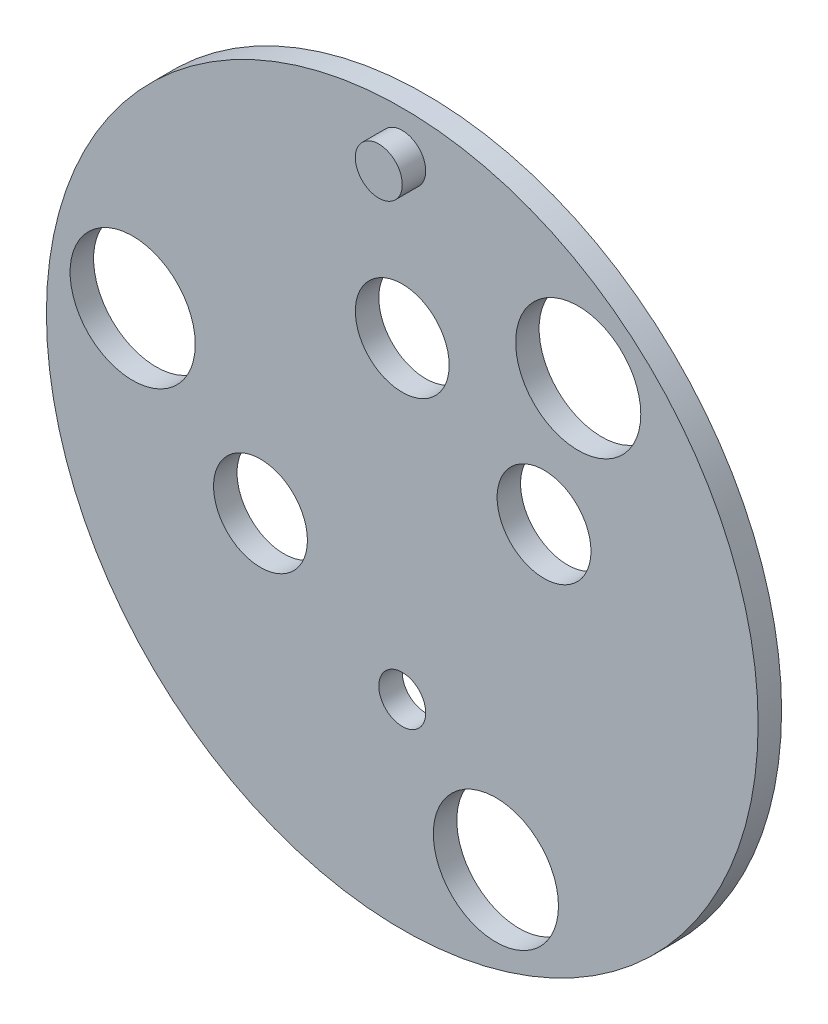
SolidWorks part; units mm, degrees
ref_plane "Front Plane" through (0, 0, 0) normal (0, 0, 1) x (1, 0, 0)
ref_plane "Top Plane" through (0, 0, 0) normal (0, 1, 0) x (1, 0, 0)
ref_plane "Right Plane" through (0, 0, 0) normal (1, 0, 0) x (0, 0, -1)
sketch "Sketch1" plane through (0, 0, 0) normal (0, 0, 1) x (1, 0, 0)
  circle A0 centre (0, 0) radius 227.5
  circle A1 centre (0, 200) radius 15
  point P5 (10.2659, 199.7364)
  dimension "D2" = 30
  dimension "D3" = 455
  dimension "D1" = 200
extrude "Boss-Extrude1" add sketch "Sketch1" along normal mid plane 15 contours A0
extrude "Boss-Extrude2" add sketch "Sketch1<3>" along normal blind 15 from surface contours A1 region at (0, 200, 0) starting at face at (227.5, 0, 7.5)
sketch "Sketch1<3>" plane through (0, 0, 0) normal (0, 0, 1) x (1, 0, 0) same geometry as "Sketch1"
sketch "Sketch2" plane through (0, 0, 7.5) normal (0, 0, 1) x (1, 0, 0)
  line L0 (90.6308, 42.2618) -> (-90.6308, -42.2618) construction
  line L1 (0, -100) -> (0, 100) construction
  line L2 (-172.3414, 30.3884) -> (0, 0) construction
  line L3 (59.8535, -164.4462) -> (0, 0) construction
  line L4 (0, 0) -> (112.4878, 134.0578) construction
  circle A0 centre (-172.3414, 30.3884) radius 40
  circle A2 centre (0, 100) radius 30
  circle A4 centre (90.6308, 42.2618) radius 30
  circle A6 centre (0, -100) radius 15
  circle A9 centre (-90.6308, -42.2618) radius 30
  circle A10 centre (112.4878, 134.0578) radius 40
  circle A11 centre (59.8535, -164.4462) radius 40
  dimension "D1" = 60
  dimension "D4" = 100
  dimension "D5" = 30
  dimension "D8" = 60
  dimension "D11" = 3
  dimension "D12" = 120
  dimension "D7" = 80
  dimension "D2" = 100
  dimension "D6" = 175
  dimension "D3" = 100
  dimension "D9" = 115
  dimension "D10" = 80
  dimension "D13" = 120
extrude "Cut-Extrude1" cut sketch "Sketch2" against normal through all
